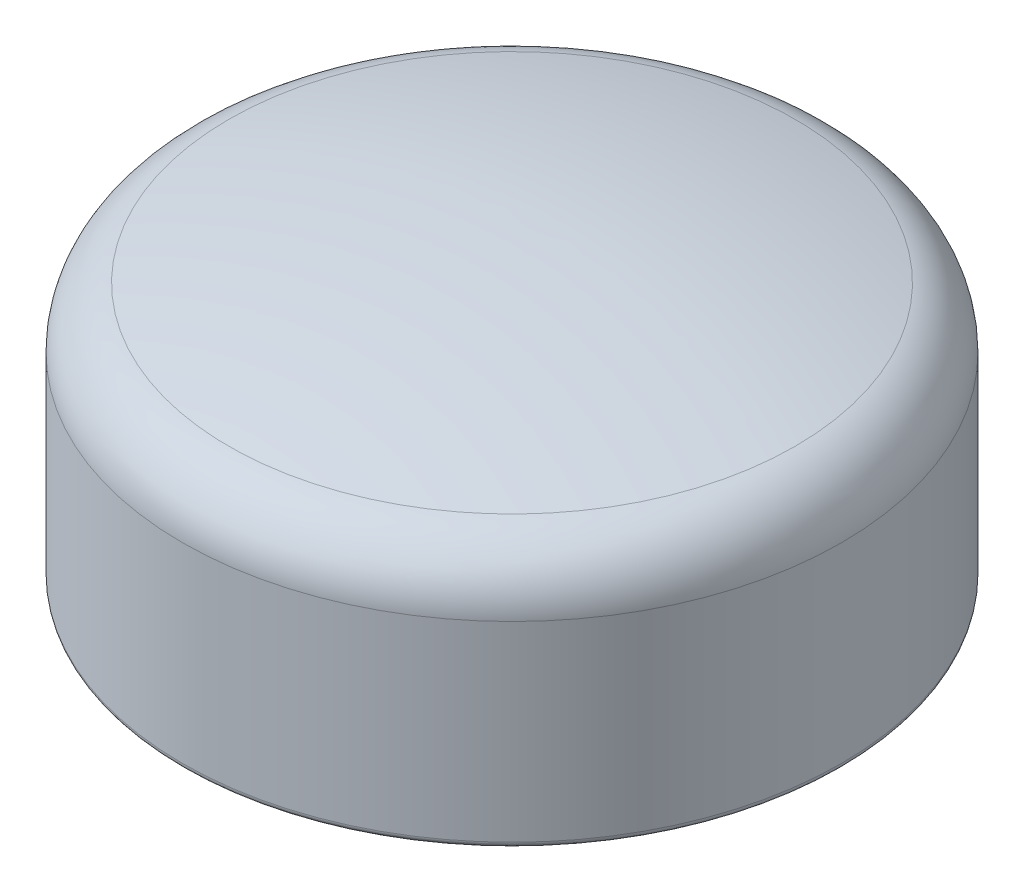
SolidWorks part; units mm, degrees
material "Nylon 101"
ref_plane "Front Plane" through (0, 0, 0) normal (0, 0, 1) x (1, 0, 0)
ref_plane "Top Plane" through (0, 0, 0) normal (0, 1, 0) x (1, 0, 0)
ref_plane "Right Plane" through (0, 0, 0) normal (1, 0, 0) x (0, 0, -1)
sketch "Sketch1" plane through (0, 0, 0) normal (0, 0, 1) x (1, 0, 0)
  line L0 (0, -281.8326) -> (0, 13809.795) construction
  line L1 (13.5, 8.081) -> (13.5, 0)
  line L2 (13.5, 0) -> (12.5, 0)
  line L3 (12.5, 0) -> (12.5, 8.081)
  line L4 (0, 12.081) -> (0, 11.081)
  line L5 (13.5, 10) -> (13.5, 8.081) construction
  line L6 (11.344, 9.5875) -> (11.6028, 10.5534) construction
  line L7 (11.344, 9.5875) -> (2.2489, 12.0245) construction
  arc A1 (11.344, 9.5875) -> (0, 11.081) centre (0, -32.7488) ccw
  arc A2 (12.5, 8.081) -> (11.344, 9.5875) centre (10.9403, 8.081) ccw
  arc A3 (11.6028, 10.5534) -> (0, 12.081) centre (0, -32.7488) ccw
  arc A4 (13.5, 8.081) -> (11.6028, 10.5534) centre (10.9403, 8.081) ccw
  arc A5 (13.5, 10) -> (11.6028, 10.5534) centre (0, -32.7488) ccw construction
  point P10 (13.0075, 1.1228)
  point P16 (0, 0)
  point P17 (17.0926, 0.955)
  point P18 (0, 0)
  dimension "D1" = 25
  dimension "D6" = 15
  dimension "D2" = 1
  dimension "D3" = 10
  dimension "D4" = 3
  dimension "D5" = 1
revolve "Revolve1" add sketch "Sketch1" angle 360 about L0
fillet "Fillet1" radius 0.25 2 edges at (12.5, 0, 0) (13.5, 0, 0)
